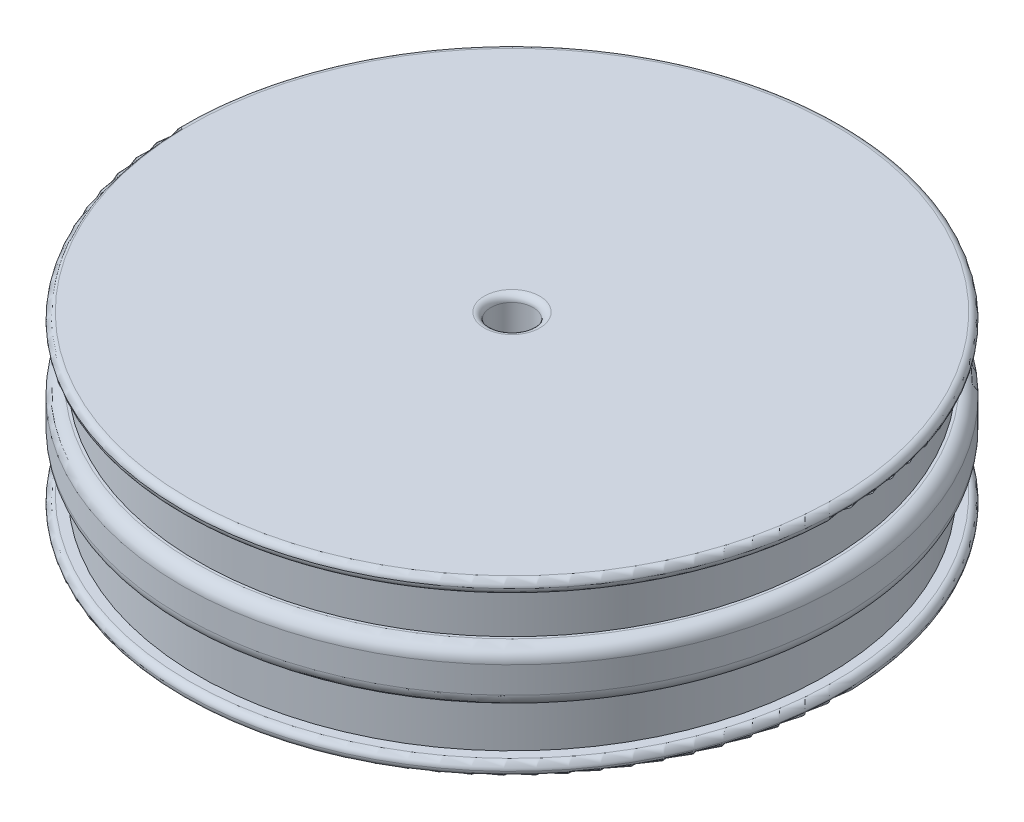
SolidWorks part; units mm, degrees
ref_plane "Front Plane" through (0, 0, 0) normal (0, 0, 1) x (1, 0, 0)
ref_plane "Top Plane" through (0, 0, 0) normal (0, 1, 0) x (1, 0, 0)
ref_plane "Right Plane" through (0, 0, 0) normal (1, 0, 0) x (0, 0, -1)
sketch "Sketch1" plane through (0, 0, 0) normal (0, 1, 0) x (1, 0, 0)
  circle A0 centre (0, 0) radius 25
  circle A1 centre (0, 0) radius 1.6
  dimension "D1" = 3.2
  dimension "D2" = 50
extrude "Boss-Extrude1" add sketch "Sketch1" along normal blind 13
sketch "Sketch3" plane through (0, 0, 0) normal (1, 0, 0) x (0, 0, -1)
  line L0 (-25, 13) -> (-25, 0) construction
  line L1 (-25, 12) -> (-23.8, 12)
  line L2 (-25, 12) -> (-25, 8.5)
  line L3 (-25, 8.5) -> (-23.8, 8.5)
  line L4 (-23.8, 12) -> (-23.8, 8.5)
  line L7 (-25, 4.5) -> (-23.8, 4.5)
  line L8 (-25, 4.5) -> (-25, 1)
  line L9 (-25, 1) -> (-23.8, 1)
  line L10 (-23.8, 4.5) -> (-23.8, 1)
  line L11 (55, 0) -> (-55, 0) construction
  line L12 (25, 13) -> (-25, 13) construction
  line L13 (0, -0.5434) -> (0, 15.7056) construction
  line L14 (0, 55) -> (0, -55) construction
  dimension "D1" = 1
  dimension "D2" = 3.5
  dimension "D3" = 1
  dimension "D4" = 1.2
revolve "Cut-Revolve1" cut sketch "Sketch3" angle 360 about L13
fillet "Fillet1" radius 1 2 edges at (0, 4.5, -25) (0, 8.5, -25)
fillet "Fillet2" radius 0.5 2 edges at (0, 12, -25) (0, 1, -25)
fillet "Fillet3" radius 0.5 2 edges at (0, 0, 25) (0, 13, 25)
fillet "Fillet4" radius 0.5 2 edges at (0, 0, 1.6) (0, 13, 1.6)
